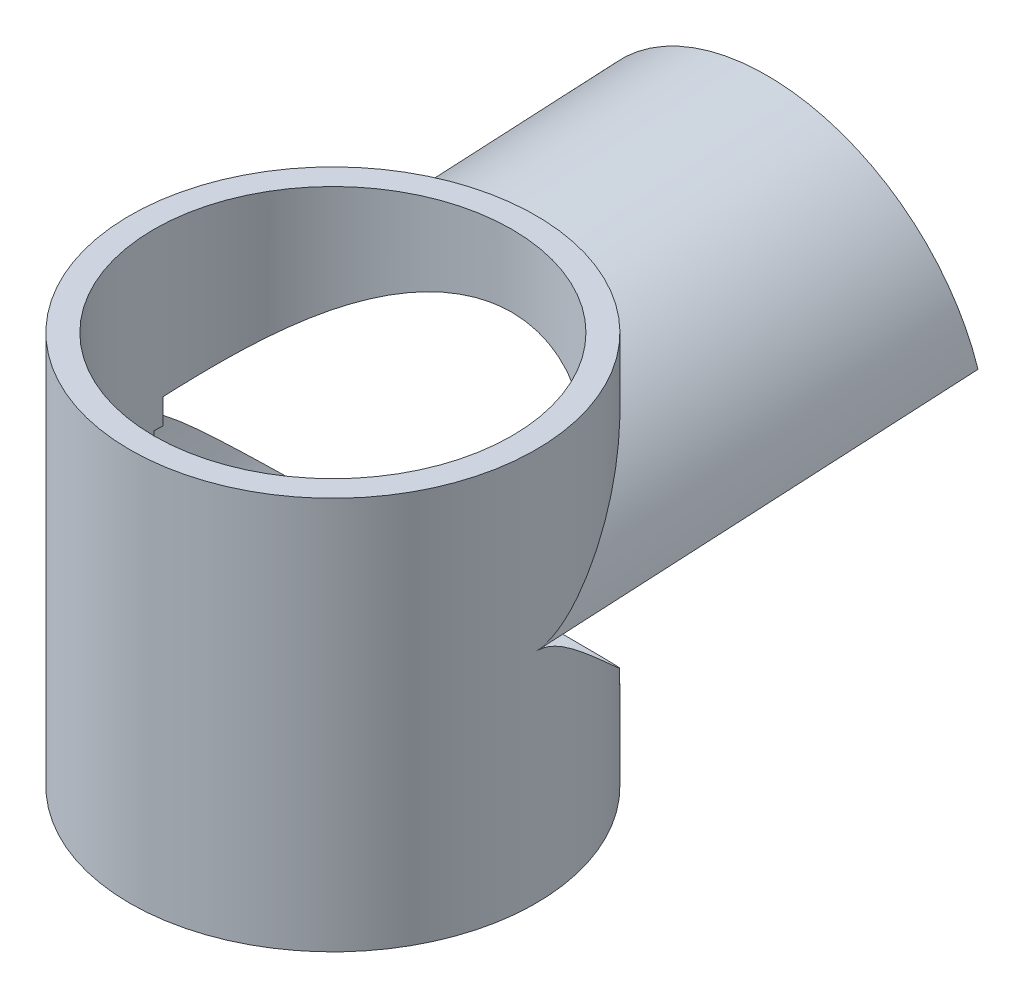
SolidWorks part; units mm, degrees
ref_plane "Front Plane" through (0, 0, 0) normal (0, 0, 1) x (1, 0, 0)
ref_plane "Top Plane" through (0, 0, 0) normal (0, 1, 0) x (1, 0, 0)
ref_plane "Right Plane" through (0, 0, 0) normal (1, 0, 0) x (0, 0, -1)
sketch "Sketch1" plane through (0, 0, 0) normal (0, 1, 0) x (1, 0, 0)
  circle A0 centre (0, 0) radius 20.5
  circle A1 centre (0, 0) radius 23.25
  dimension "D1" = 41
  dimension "D2" = 46.5
extrude "Boss-Extrude1" add sketch "Sketch1" along normal blind 40
extrude "Boss-Extrude2" add sketch "Sketch1<2>" against normal blind 5 contours A0 | A1 A0 region at (0, 0, 0) region at (-22.5924, 0, 0)
sketch "Sketch1<2>" plane through (0, 0, 0) normal (0, 1, 0) x (1, 0, 0) same geometry as "Sketch1"
sketch "Sketch2" plane through (0, 0, 0) normal (0, 0, 1) x (1, 0, 0)
  line L2 (23.25, 20) -> (-23.25, 20)
  line L3 (-23.25, 40) -> (-23.25, -5) construction
  line L4 (23.25, -5) -> (23.25, 40) construction
  arc A0 (-23.25, 20) -> (23.25, 20) centre (0, 23.5141) ccw
  dimension "D1" = 20
extrude "Cut-Extrude1" cut sketch "Sketch2" against normal blind 35 contours L2 A0 region at (0, 11.6102, 0)
sketch3d "3DSketch1"
  line L0 (0, 20, -23.25) -> (0, 21.4392, -50.7123)
  line L1 (0, 20, -22.5892) -> (0, 20, -50022.5892) construction
  arc A0 (23.25, 20, 0) -> (-23.25, 20, 0) centre (0, 20, 0) ccw construction
  arc A1 (23.25, 20, 0) -> (-23.25, 20, 0) centre (0, 20, 0) ccw
  point P3 (0, 43.25, 0)
  point P4 (0, 43.25, 0)
  dimension "D1" = 3
  dimension "D2" = 27.5
sketch "Sketch3" plane through (0, 2.7092, -51.6939) normal (0, -0.0523, 0.9986) x (1, 0, 0)
  line L0 (0, 10485.9816) -> (0, -13065.1987) construction
  arc A0 (-23.25, 19.9726) -> (23.25, 19.9726) centre (0, 0) cw
  arc A1 (23.25, 19.9726) -> (-23.25, 19.9726) centre (0, 14.0197) ccw
  ellipse E0 centre (0, 19.9726) end of major axis (23.25, 19.9726) minor radius 1.2168 (-23.25, 19.9726) -> (23.25, 19.9726) ccw construction
  ellipse E1 centre (0, 19.9726) end of major axis (23.25, 19.9726) minor radius 1.2168 (-23.25, 19.9726) -> (23.25, 19.9726) ccw
  dimension "D1" = 24
extrude "Boss-Extrude3" add sketch "Sketch3" along normal up to body separate body contours A0 A1 region at (0, 34.1012, -50.0487)
sketch "Sketch4" plane through (0, 2.7092, -51.6939) normal (0, -0.0523, 0.9986) x (1, 0, 0)
  arc A1 (23.25, 19.9726) -> (-23.25, 19.9726) centre (0, 0) ccw
  arc A2 (23.25, 19.9726) -> (-23.25, 19.9726) centre (0, 0) ccw
  ellipse E1 centre (0, 19.9726) end of major axis (23.25, 19.9726) minor radius 1.2168 (-23.25, 19.9726) -> (23.25, 19.9726) ccw
  ellipse E2 centre (0, 19.9726) end of major axis (23.25, 19.9726) minor radius 1.2168 (-23.25, 19.9726) -> (23.25, 19.9726) ccw
  dimension "D1" = 0
extrude "Cut-Extrude5" cut sketch "Sketch4" along normal offset from surface 1 separate body contours A2 E2 region at (0, 26.4365, -50.4504) up to face at (-21.5377, 17.2905, 0)
sketch "Sketch5" plane through (0, 0, 0) normal (0, 1, 0) x (1, 0, 0)
  circle A0 centre (0, 0) radius 1.25
  dimension "D1" = 2.5
extrude "Cut-Extrude6" cut sketch "Sketch5" against normal blind 10 contours A0
